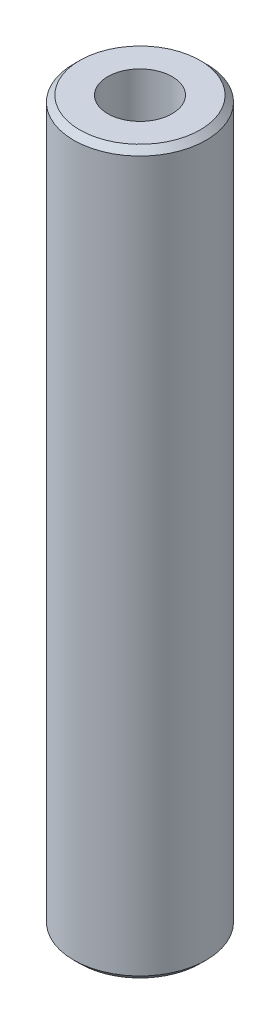
SolidWorks part; units mm, degrees
ref_plane "Front Plane" through (0, 0, 0) normal (0, 0, 1) x (1, 0, 0)
ref_plane "Top Plane" through (0, 0, 0) normal (0, 1, 0) x (1, 0, 0)
ref_plane "Right Plane" through (0, 0, 0) normal (1, 0, 0) x (0, 0, -1)
sketch "Sketch1" plane through (0, 0, 0) normal (0, 1, 0) x (1, 0, 0)
  circle A0 centre (0, 0) radius 55
  dimension "SHAFT_OD" = 110
extrude "Boss-Extrude1" add sketch "Sketch1" along normal blind 600
sketch "Sketch2" plane through (0, 0, 0) normal (0, 1, 0) x (1, 0, 0)
  circle A0 centre (0, 0) radius 26.7512
  dimension "BORE_D" = 53.5023
extrude "Cut-Extrude1" cut sketch "Sketch2" along normal through all
chamfer "Chamfer1" distance 4.9695 angle 45 2 edges at (0, 600, 55) (0, 0, 55)
